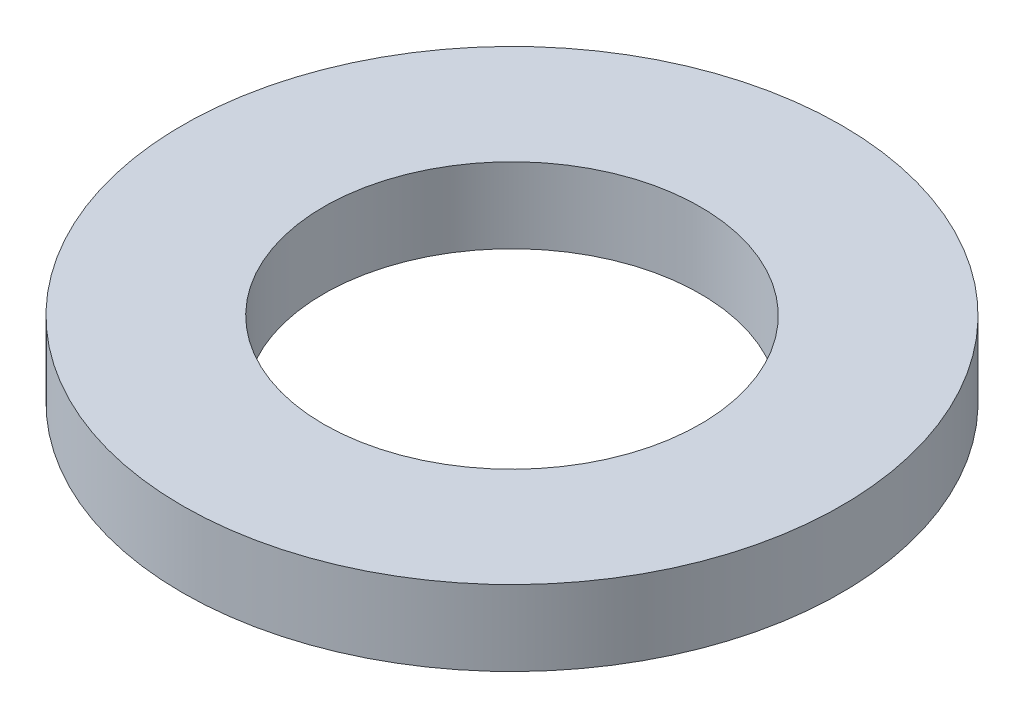
SolidWorks part; units mm, degrees
ref_plane "Front Plane" through (0, 0, 0) normal (0, 0, 1) x (1, 0, 0)
ref_plane "Top Plane" through (0, 0, 0) normal (0, 1, 0) x (1, 0, 0)
ref_plane "Right Plane" through (0, 0, 0) normal (1, 0, 0) x (0, 0, -1)
sketch "Sketch1" plane through (0, 0, 0) normal (0, 1, 0) x (1, 0, 0)
  circle A0 centre (0, 0) radius 17.5
  dimension "FLANGE_OD" = 35
extrude "Boss-Extrude1" add sketch "Sketch1" along normal blind 4
sketch "Sketch2" plane through (0, 0, 0) normal (0, 1, 0) x (1, 0, 0)
  circle A0 centre (0, 0) radius 10
  dimension "BORE_D" = 20
extrude "Cut-Extrude1" cut sketch "Sketch2" along normal through all
sketch "Sketch3" plane through (0, 4, 0) normal (0, 1, 0) x (1, 0, 0)
  circle A0 centre (0, 0) radius 6.3892 construction
  circle A1 centre (-6.3892, 0) radius 1.5
  dimension "BOLT_D" = 3
  dimension "BOLT_PCD" = 12.7783
extrude "Cut-Extrude2" cut sketch "Sketch3" against normal blind 3.6794 rebuild error yes
pattern_circular "CirPattern1" count 5 over 360 rebuild error yes
